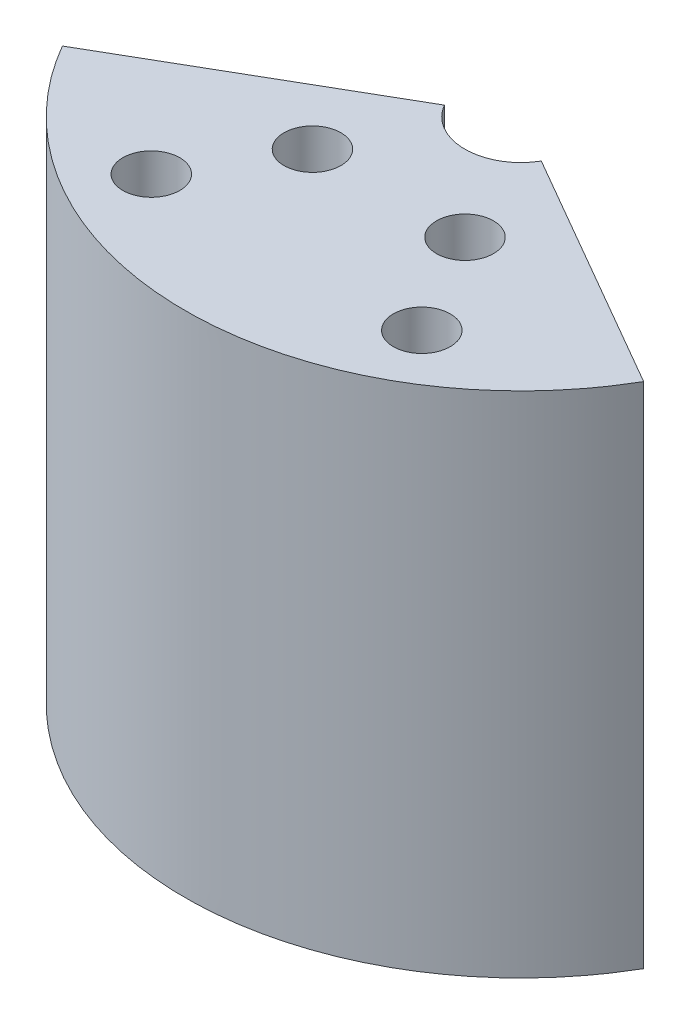
SolidWorks part; units mm, degrees
note: '?' marks a value the reader was unsure of.
ref_plane "Front Plane" through (0, 0, 0) normal (0, 0, 1) x (1, 0, 0)
ref_plane "Top Plane" through (0, 0, 0) normal (0, 1, 0) x (1, 0, 0)
ref_plane "Right Plane" through (0, 0, 0) normal (1, 0, 0) x (0, 0, -1)
curve "Curve1"
  spline degree 1 poles (-18.75, -123.736, 32.476) (-22.25, -123.736, 38.538) knots 0 0 1 1
curve "Curve2"
  spline degree 1 poles (-18.75, 1.256, 32.476) (-22.25, 1.256, 38.538) knots 0 0 1 1
curve "Curve3"
  spline degree 1 poles (-33.25, -123.736, 57.591) (-36.75, -123.736, 63.653) knots 0 0 1 1
curve "Curve4"
  spline degree 1 poles (-33.25, 1.256, 57.591) (-36.75, 1.256, 63.653) knots 0 0 1 1
curve "Curve5"
  spline degree 1 poles (18.75, -123.736, 32.476) (22.25, -123.736, 38.538) knots 0 0 1 1
curve "Curve6"
  spline degree 1 poles (18.75, 1.256, 32.476) (22.25, 1.256, 38.538) knots 0 0 1 1
curve "Curve7"
  spline degree 1 poles (33.25, -123.736, 57.591) (36.75, -123.736, 63.653) knots 0 0 1 1
curve "Curve8"
  spline degree 1 poles (33.25, 1.256, 57.591) (36.75, 1.256, 63.653) knots 0 0 1 1
curve "Curve9"
  spline degree 3 poles (37.4383, 1.256, -2.6473) (37.5308, 1.256, 0) (37.4383, 1.256, 2.6473) (37.1578, 1.256, 5.2815) (36.6924, 1.256, 7.8892) (36.0449, 1.256, 10.4581) (35.2172, 1.256, 12.9746) (34.2146, 1.256, 15.4269) (33.0405, 1.256, 17.8016) (31.7019, 1.256, 20.0876) (30.2075, 1.256, 22.2745) (28.5607, 1.256, 24.3495) (26.7709, 1.256, 26.3024) (24.85, 1.256, 28.1265) (22.8037, 1.256, 29.8088) (20.6442, 1.256, 31.3428) (18.3823, 1.256, 32.7214) (16.028, 1.256, 33.936) (13.5944, 1.256, 34.9833) (11.0926, 1.256, 35.8547) (8.5358, 1.256, 36.5471) (5.9369, 1.256, 37.059) (3.3079, 1.256, 37.3849) (0.6623, 1.256, 37.5253) (-1.9863, 1.256, 37.4779) (-4.6252, 1.256, 37.2452) (-7.2405, 1.256, 36.8252) (-9.8207, 1.256, 36.2245) (-12.351, 1.256, 35.4403) (-14.8202, 1.256, 34.4807) (-17.2154, 1.256, 33.3495) (-19.5253, 1.256, 32.053) (-21.737, 1.256, 30.5949) (-23.842, 1.256, 28.9866) (-25.8263, 1.256, 27.2314) (-27.6829, 1.256, 25.3418) (-29.4025, 1.256, 23.3269) (-30.9737, 1.256, 21.1941) (-32.3917, 1.256, 18.9567) (-33.6493, 1.256, 16.6251) (-34.7367, 1.256, 14.2095) (-35.6524, 1.256, 11.7238) (-36.3916, 1.256, 9.1797) (-36.9473, 1.256, 6.5896) (-37.3212, 1.256, 3.9669) (-37.5081, 1.256, 1.3246) (-37.5081, 1.256, -1.3246) (-37.3212, 1.256, -3.9669) (-36.9473, 1.256, -6.5896) (-36.3916, 1.256, -9.1797) (-35.6524, 1.256, -11.7238) (-34.7367, 1.256, -14.2095) (-33.6493, 1.256, -16.6251) (-32.3917, 1.256, -18.9567) (-30.9737, 1.256, -21.1941) (-29.4025, 1.256, -23.3269) (-27.6829, 1.256, -25.3418) (-25.8263, 1.256, -27.2314) (-23.842, 1.256, -28.9866) (-21.737, 1.256, -30.5949) (-19.5253, 1.256, -32.053) (-17.2154, 1.256, -33.3495) (-14.8202, 1.256, -34.4807) (-12.351, 1.256, -35.4403) (-9.8207, 1.256, -36.2245) (-7.2405, 1.256, -36.8252) (-4.6252, 1.256, -37.2452) (-1.9863, 1.256, -37.4779) (0.6623, 1.256, -37.5253) (3.3079, 1.256, -37.3849) (5.9369, 1.256, -37.059) (8.5358, 1.256, -36.5471) (11.0926, 1.256, -35.8547) (13.5944, 1.256, -34.9833) (16.028, 1.256, -33.936) (18.3823, 1.256, -32.7214) (20.6442, 1.256, -31.3428) (22.8037, 1.256, -29.8088) (24.85, 1.256, -28.1265) (26.7709, 1.256, -26.3024) (28.5607, 1.256, -24.3495) (30.2075, 1.256, -22.2745) (31.7019, 1.256, -20.0876) (33.0405, 1.256, -17.8016) (34.2146, 1.256, -15.4269) (35.2172, 1.256, -12.9746) (36.0449, 1.256, -10.4581) (36.6924, 1.256, -7.8892) (37.1578, 1.256, -5.2815) (37.4383, 1.256, -2.6473) (37.5308, 1.256, 0) (37.4383, 1.256, 2.6473) knots -0.033708 -0.022471 -0.011235 0 0.011235 0.022471 0.033708 0.044942 0.05618 0.067417 0.078654 0.089888 0.101125 0.112359 0.123596 0.134832 0.146066 0.157303 0.168537 0.179773 0.191011 0.20225 0.213482 0.224718 0.235955 0.24719 0.258429 0.269662 0.2809 0.292133 0.303372 0.314608 0.325842 0.337078 0.348313 0.35955 0.370786 0.382022 0.393259 0.404492 0.415729 0.426966 0.4382 0.449437 0.460674 0.471911 0.483145 0.494384 0.505616 0.516855 0.528089 0.539326 0.550563 0.5618 0.573034 0.584271 0.595508 0.606741 0.617978 0.629214 0.64045 0.651687 0.662922 0.674158 0.685392 0.696628 0.707867 0.7191 0.730338 0.741571 0.75281 0.764045 0.775282 0.786518 0.79775 0.808989 0.820227 0.831463 0.842697 0.853934 0.865168 0.876404 0.887641 0.898875 0.910112 0.921346 0.932583 0.94382 0.955058 0.966292 0.977529 0.988765 1 1.011235 1.022471 1.033708 periodic
curve "Curve11"
  spline degree 3 poles (71.447, -123.736, 41.25) (70.418, -123.736, 42.9493) (68.3601, -123.736, 46.3475) (64.8175, -123.736, 51.1464) (60.9634, -123.736, 55.6938) (56.7843, -123.736, 59.947) (52.3103, -123.736, 63.8874) (47.5642, -123.736, 67.4957) (42.5701, -123.736, 70.7526) (37.3536, -123.736, 73.6398) (31.9427, -123.736, 76.1434) (26.3649, -123.736, 78.2488) (20.6501, -123.736, 79.9472) (14.8278, -123.736, 81.23) (8.9275, -123.736, 82.0871) (2.9811, -123.736, 82.5178) (-2.9811, -123.736, 82.5178) (-8.9275, -123.736, 82.0871) (-14.8278, -123.736, 81.23) (-20.6501, -123.736, 79.9472) (-26.3649, -123.736, 78.2488) (-31.9427, -123.736, 76.1434) (-37.3536, -123.736, 73.6398) (-42.5701, -123.736, 70.7526) (-47.5642, -123.736, 67.4957) (-52.3103, -123.736, 63.8874) (-56.7843, -123.736, 59.947) (-60.9634, -123.736, 55.6938) (-64.8175, -123.736, 51.1464) (-68.3601, -123.736, 46.3475) (-70.418, -123.736, 42.9493) (-71.447, -123.736, 41.25) knots 0 0 0 0 0.034484 0.068962 0.10345 0.137933 0.172414 0.206896 0.241381 0.275866 0.310346 0.344829 0.379312 0.413791 0.448275 0.482761 0.517239 0.551725 0.586209 0.620688 0.655171 0.689654 0.724134 0.758619 0.793104 0.827586 0.862067 0.89655 0.931038 0.965516 1 1 1 1
curve "Curve13"
  spline degree 3 poles (11.908, -123.736, 6.875) (11.7366, -123.736, 7.1582) (11.3937, -123.736, 7.7246) (10.8024, -123.736, 8.5235) (10.1614, -123.736, 9.2826) (9.4638, -123.736, 9.9905) (8.7188, -123.736, 10.6482) (7.9279, -123.736, 11.25) (7.095, -123.736, 11.7921) (6.2258, -123.736, 12.2738) (5.3233, -123.736, 12.6898) (4.3941, -123.736, 13.0412) (3.4418, -123.736, 13.3249) (2.4713, -123.736, 13.5375) (1.4879, -123.736, 13.6809) (0.497, -123.736, 13.753) (-0.497, -123.736, 13.753) (-1.4879, -123.736, 13.6809) (-2.4713, -123.736, 13.5375) (-3.4418, -123.736, 13.3249) (-4.3941, -123.736, 13.0412) (-5.3233, -123.736, 12.6898) (-6.2258, -123.736, 12.2738) (-7.095, -123.736, 11.7921) (-7.9279, -123.736, 11.25) (-8.7188, -123.736, 10.6482) (-9.4638, -123.736, 9.9905) (-10.1614, -123.736, 9.2826) (-10.8024, -123.736, 8.5235) (-11.3937, -123.736, 7.7246) (-11.7366, -123.736, 7.1582) (-11.908, -123.736, 6.875) knots 0 0 0 0 0.034471 0.068962 0.103437 0.137919 0.172419 0.206895 0.241383 0.27588 0.310349 0.344841 0.379303 0.413796 0.448263 0.482773 0.517227 0.551737 0.586204 0.620697 0.655159 0.689651 0.72412 0.758617 0.793105 0.827581 0.862081 0.896563 0.931038 0.965529 1 1 1 1
curve "Curve15"
  spline degree 1 poles (71.447, -123.736, 41.25) (11.908, -123.736, 6.875) knots 0 0 1 1
curve "Curve18"
  spline degree 1 poles (-71.447, -123.736, 41.25) (-11.908, -123.736, 6.875) knots 0 0 1 1
curve "Curve20"
  spline degree 1 poles (0, 1.256, 0) (6.761, 1.256, 82.222) knots 0 0 1 1
curve "Curve21"
  spline degree 1 poles (67.826, 1.256, -46.967) (0, 1.256, 0) knots 0 0 1 1
ref_plane "Plane1" through (0, 1.256, 0) normal (0, 1, 0) x (-0.6346, 0, -0.7728)
sketch3d "3DSketch2"
  line L1 (-18.75, -123.736, 32.476) -> (-22.25, -123.736, 38.538)
  line L2 (-18.75, -123.736, 32.476) -> (-22.25, -123.736, 38.538)
  line L3 (71.447, -123.736, 41.25) -> (11.908, -123.736, 6.875)
  line L4 (71.447, -123.736, 41.25) -> (11.908, -123.736, 6.875)
  line L5 (-71.447, -123.736, 41.25) -> (-11.908, -123.736, 6.875)
  line L6 (-71.447, -123.736, 41.25) -> (-11.908, -123.736, 6.875)
  line L7 (18.75, -123.736, 32.476) -> (22.25, -123.736, 38.538)
  line L8 (18.75, -123.736, 32.476) -> (22.25, -123.736, 38.538)
  line L9 (33.25, -123.736, 57.591) -> (36.75, -123.736, 63.653)
  line L10 (33.25, -123.736, 57.591) -> (36.75, -123.736, 63.653)
  line L11 (-33.25, -123.736, 57.591) -> (-36.75, -123.736, 63.653)
  line L12 (-33.25, -123.736, 57.591) -> (-36.75, -123.736, 63.653)
  circle A0 centre (-18.75, -123.736, 32.476) radius 6.9998
  circle A1 centre (-33.25, -123.736, 57.591) radius 6.9998
  circle A2 centre (18.75, -123.736, 32.476) radius 6.9998
  circle A3 centre (33.25, -123.736, 57.591) radius 6.9998
  spline S2 degree 3 poles (1827.4215, -123.736, 993.494) (68.4784, -123.736, -91.3476) (101.4416, -123.736, 1.534) (64.8175, -123.736, 51.1464) (60.9634, -123.736, 55.6938) (56.7843, -123.736, 59.947) (52.3103, -123.736, 63.8874) (47.5642, -123.736, 67.4957) (42.5701, -123.736, 70.7526) (37.3536, -123.736, 73.6398) (31.9427, -123.736, 76.1434) (26.3649, -123.736, 78.2488) (20.6501, -123.736, 79.9472) (14.8278, -123.736, 81.23) (8.9275, -123.736, 82.0871) (2.9811, -123.736, 82.5178) (-2.9811, -123.736, 82.5178) (-8.9275, -123.736, 82.0871) (-14.8278, -123.736, 81.23) (-20.6501, -123.736, 79.9472) (-26.3649, -123.736, 78.2488) (-31.9427, -123.736, 76.1434) (-37.3536, -123.736, 73.6398) (-42.5701, -123.736, 70.7526) (-47.5642, -123.736, 67.4957) (-52.3103, -123.736, 63.8874) (-56.7843, -123.736, 59.947) (-60.9634, -123.736, 55.6938) (-64.8175, -123.736, 51.1464) (-101.4416, -123.736, 1.534) (-68.4785, -123.736, -91.3475) (-1827.4184, -123.736, 993.4921) knots -0.966044 -0.966044 -0.966044 -0.966044 0.034484 0.068962 0.10345 0.137933 0.172414 0.206896 0.241381 0.275866 0.310346 0.344829 0.379312 0.413791 0.448275 0.482761 0.517239 0.551725 0.586209 0.620688 0.655171 0.689654 0.724134 0.758619 0.793104 0.827586 0.862067 0.89655 0.931038 0.965516 1.966043 1.966043 1.966043 1.966043 only from (71.447, -123.736, 41.25) to (-71.447, -123.736, 41.25)
  spline S3 degree 3 poles (71.447, -123.736, 41.25) (70.418, -123.736, 42.9493) (68.3601, -123.736, 46.3475) (64.8175, -123.736, 51.1464) (60.9634, -123.736, 55.6938) (56.7843, -123.736, 59.947) (52.3103, -123.736, 63.8874) (47.5642, -123.736, 67.4957) (42.5701, -123.736, 70.7526) (37.3536, -123.736, 73.6398) (31.9427, -123.736, 76.1434) (26.3649, -123.736, 78.2488) (20.6501, -123.736, 79.9472) (14.8278, -123.736, 81.23) (8.9275, -123.736, 82.0871) (2.9811, -123.736, 82.5178) (-2.9811, -123.736, 82.5178) (-8.9275, -123.736, 82.0871) (-14.8278, -123.736, 81.23) (-20.6501, -123.736, 79.9472) (-26.3649, -123.736, 78.2488) (-31.9427, -123.736, 76.1434) (-37.3536, -123.736, 73.6398) (-42.5701, -123.736, 70.7526) (-47.5642, -123.736, 67.4957) (-52.3103, -123.736, 63.8874) (-56.7843, -123.736, 59.947) (-60.9634, -123.736, 55.6938) (-64.8175, -123.736, 51.1464) (-68.3601, -123.736, 46.3475) (-70.418, -123.736, 42.9493) (-71.447, -123.736, 41.25) knots 0 0 0 0 0.034484 0.068962 0.10345 0.137933 0.172414 0.206896 0.241381 0.275866 0.310346 0.344829 0.379312 0.413791 0.448275 0.482761 0.517239 0.551725 0.586209 0.620688 0.655171 0.689654 0.724134 0.758619 0.793104 0.827586 0.862067 0.89655 0.931038 0.965516 1 1 1 1
  spline S4 degree 3 poles (1709.6301, -123.736, 1063.5563) (-3.8827, -123.736, -43.2406) (21.3808, -123.736, -5.7669) (10.8024, -123.736, 8.5235) (10.1614, -123.736, 9.2826) (9.4638, -123.736, 9.9905) (8.7188, -123.736, 10.6482) (7.9279, -123.736, 11.25) (7.095, -123.736, 11.7921) (6.2258, -123.736, 12.2738) (5.3233, -123.736, 12.6898) (4.3941, -123.736, 13.0412) (3.4418, -123.736, 13.3249) (2.4713, -123.736, 13.5375) (1.4879, -123.736, 13.6809) (0.497, -123.736, 13.753) (-0.497, -123.736, 13.753) (-1.4879, -123.736, 13.6809) (-2.4713, -123.736, 13.5375) (-3.4418, -123.736, 13.3249) (-4.3941, -123.736, 13.0412) (-5.3233, -123.736, 12.6898) (-6.2258, -123.736, 12.2738) (-7.095, -123.736, 11.7921) (-7.9279, -123.736, 11.25) (-8.7188, -123.736, 10.6482) (-9.4638, -123.736, 9.9905) (-10.1614, -123.736, 9.2826) (-10.8024, -123.736, 8.5235) (-21.3809, -123.736, -5.767) (3.883, -123.736, -43.241) (-1709.6639, -123.736, 1063.5782) knots -1.746773 -1.746773 -1.746773 -1.746773 0.034471 0.068962 0.103437 0.137919 0.172419 0.206895 0.241383 0.27588 0.310349 0.344841 0.379303 0.413796 0.448263 0.482773 0.517227 0.551737 0.586204 0.620697 0.655159 0.689651 0.72412 0.758617 0.793105 0.827581 0.862081 0.896563 0.931038 0.965529 2.746785 2.746785 2.746785 2.746785 only from (11.908, -123.736, 6.875) to (-11.908, -123.736, 6.875)
  spline S5 degree 3 poles (11.908, -123.736, 6.875) (11.7366, -123.736, 7.1582) (11.3937, -123.736, 7.7246) (10.8024, -123.736, 8.5235) (10.1614, -123.736, 9.2826) (9.4638, -123.736, 9.9905) (8.7188, -123.736, 10.6482) (7.9279, -123.736, 11.25) (7.095, -123.736, 11.7921) (6.2258, -123.736, 12.2738) (5.3233, -123.736, 12.6898) (4.3941, -123.736, 13.0412) (3.4418, -123.736, 13.3249) (2.4713, -123.736, 13.5375) (1.4879, -123.736, 13.6809) (0.497, -123.736, 13.753) (-0.497, -123.736, 13.753) (-1.4879, -123.736, 13.6809) (-2.4713, -123.736, 13.5375) (-3.4418, -123.736, 13.3249) (-4.3941, -123.736, 13.0412) (-5.3233, -123.736, 12.6898) (-6.2258, -123.736, 12.2738) (-7.095, -123.736, 11.7921) (-7.9279, -123.736, 11.25) (-8.7188, -123.736, 10.6482) (-9.4638, -123.736, 9.9905) (-10.1614, -123.736, 9.2826) (-10.8024, -123.736, 8.5235) (-11.3937, -123.736, 7.7246) (-11.7366, -123.736, 7.1582) (-11.908, -123.736, 6.875) knots 0 0 0 0 0.034471 0.068962 0.103437 0.137919 0.172419 0.206895 0.241383 0.27588 0.310349 0.344841 0.379303 0.413796 0.448263 0.482773 0.517227 0.551737 0.586204 0.620697 0.655159 0.689651 0.72412 0.758617 0.793105 0.827581 0.862081 0.896563 0.931038 0.965529 1 1 1 1
  point P13 (-18.75, -130.7358, 32.476)
  point P15 (-33.25, -130.7358, 57.591)
  point P17 (18.75, -130.7358, 32.476)
  point P19 (33.25, -130.7358, 57.591)
  dimension "D1" = 0
  dimension "D2" = 0
  dimension "D3" = 0
  dimension "D4" = 0
  dimension "D5" = 0
  dimension "D6" = 0
  dimension "D7" = 0
  dimension "D8" = 0
extrude "Extrude3" add sketch "3DSketch2" along direction (0, 1, 0) on the side against the normal up to surface (124.992 mm away) contours L6 S5 L4 S3 | A0 | A1 | A2 | A3
ref_axis "Axis1" through (0, 14.1501, 0) along (0, -1, 0)?
ref_plane "Plane3" through (0, -123.736, 0) normal (0, 1, 0) x (-1, 0, 0)
